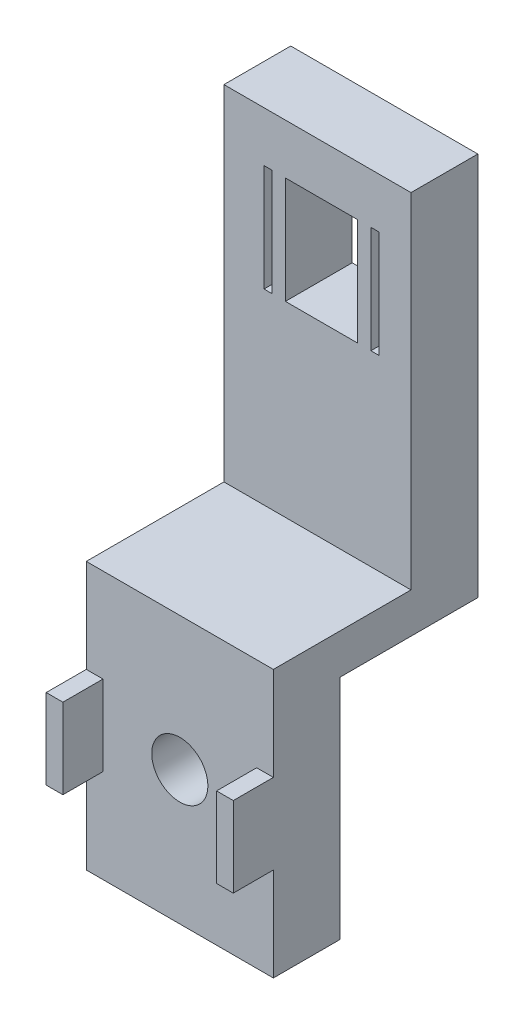
SolidWorks part; units mm, degrees
ref_plane "Front Plane" through (0, 0, 0) normal (0, 0, 1) x (1, 0, 0)
ref_plane "Top Plane" through (0, 0, 0) normal (0, 1, 0) x (1, 0, 0)
ref_plane "Right Plane" through (0, 0, 0) normal (1, 0, 0) x (0, 0, -1)
sketch "Sketch1" plane through (0, 0, 0) normal (0, 0, 1) x (1, 0, 0)
  line L0 (4.6, 42) -> (4.6, 34)
  line L1 (0, 0) -> (14, 0)
  line L2 (0, 0) -> (0, 45.75)
  line L3 (0, 45.75) -> (14, 45.75)
  line L4 (14, 0) -> (14, 45.75)
  line L9 (3, 42) -> (11.6, 42)
  line L10 (3, 42) -> (3, 34)
  line L11 (3, 34) -> (11.6, 34)
  line L12 (11.6, 42) -> (11.6, 34)
  line L13 (3.6, 42) -> (11, 42)
  line L14 (3.6, 42) -> (3.6, 34)
  line L15 (3.6, 34) -> (11, 34)
  line L16 (11, 42) -> (11, 34)
  line L17 (10, 42) -> (10, 34)
  circle A1 centre (7, 10) radius 2.1
  dimension "D7" = 4.2
  dimension "D8" = 10
  dimension "D9" = 5.4
  dimension "D1" = 14
  dimension "D2" = 45.75
  dimension "D3" = 8.6
  dimension "D4" = 8
  dimension "D5" = 42
  dimension "D6" = 2.4
  dimension "D10" = 7
  dimension "D12" = 0.6
  dimension "D13" = 0.6
  dimension "D14" = 1
  dimension "D15" = 1
extrude "Boss-Extrude3" add sketch "Sketch1" along normal blind 15.3 contours L1 L4 L3 L2 A1 L9 L13 L12 L11 L15 L10 | L9 L14 L11 L0 | L13 L17 L15 L16 region at (4.1, 38, 0) region at (10.5, 38, 0) region at (6.963, 21.3294, 0)
sketch "Sketch2" plane through (0, 0, 0) normal (-1, 0, 0) x (0, 0, 1)
  line L0 (15.3, 0) -> (15.3, 45.75) construction
  line L1 (0, 0) -> (10.3, 0)
  line L2 (0, 0) -> (0, 17)
  line L3 (0, 17) -> (10.3, 17)
  line L4 (10.3, 0) -> (10.3, 17)
  line L5 (15.3, 45.75) -> (5, 45.75)
  line L6 (15.3, 45.75) -> (15.3, 20)
  line L7 (15.3, 20) -> (5, 20)
  line L8 (5, 45.75) -> (5, 20)
  line L9 (0, 0) -> (0, 45.75) construction
  line L10 (15.3, 45.75) -> (0, 45.75) construction
  dimension "D1" = 5
  dimension "D2" = 5
  dimension "D3" = 17
  dimension "D4" = 3
  dimension "D5" = 0
extrude "Cut-Extrude1" cut sketch "Sketch2" against normal blind 21
sketch "Sketch3" plane through (0, 0, 15.3) normal (0, 0, 1) x (1, 0, 0)
  line L0 (0, 0) -> (0, 20) construction
  line L1 (0, 13) -> (1.25, 13)
  line L2 (0, 13) -> (0, 7)
  line L3 (0, 7) -> (1.25, 7)
  line L4 (1.25, 13) -> (1.25, 7)
  line L5 (14, 0) -> (14, 20) construction
  line L7 (12.75, 13) -> (12.75, 7)
  line L8 (12.75, 13) -> (14, 13)
  line L9 (14, 13) -> (14, 7)
  line L10 (12.75, 7) -> (14, 7)
  point P6 (1.25, 10)
  point P9 (14, 10)
  dimension "D1" = 6
  dimension "D2" = 0
  dimension "D3" = 1.25
  dimension "D4" = 2
  dimension "D5" = 0
extrude "Boss-Extrude4" add sketch "Sketch3" along normal blind 3
